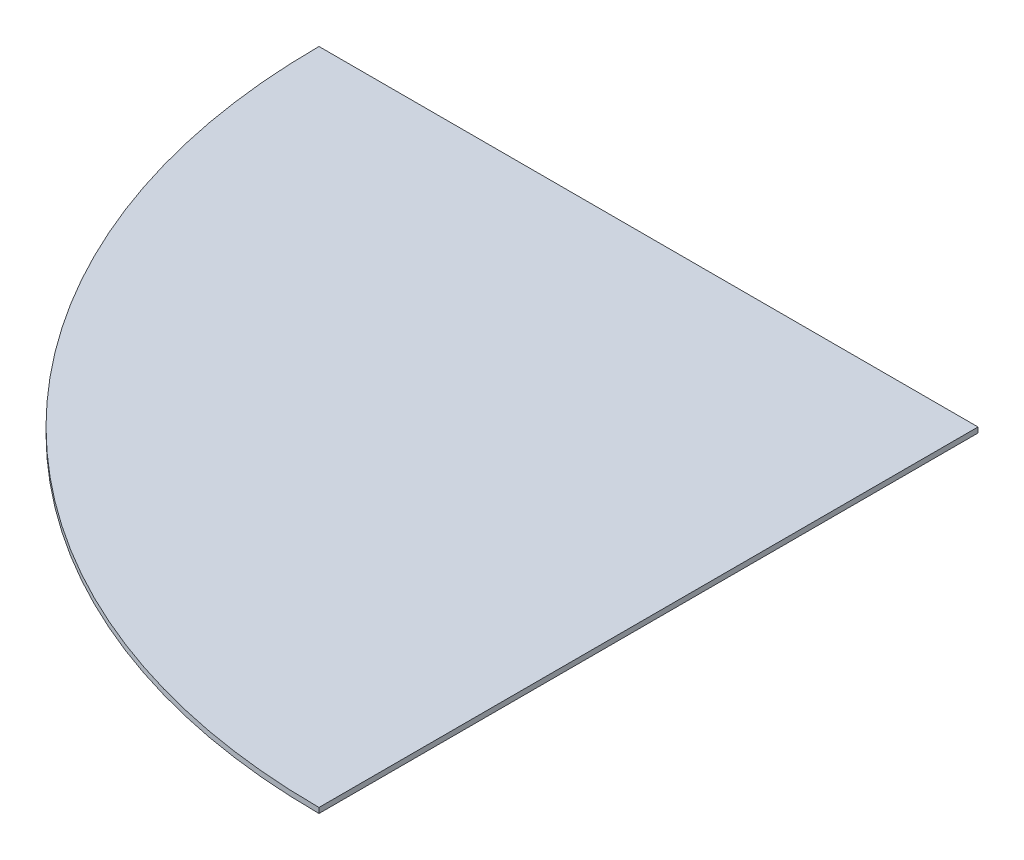
SolidWorks part; units mm, degrees
material "普通碳钢"
ref_plane "前视基准面" through (0, 0, 0) normal (0, 0, 1) x (1, 0, 0)
ref_plane "上视基准面" through (0, 0, 0) normal (0, 1, 0) x (1, 0, 0)
ref_plane "右视基准面" through (0, 0, 0) normal (1, 0, 0) x (0, 0, -1)
ref_plane "基准面1" through (0, 500, 0) normal (0, 1, 0) x (1, 0, 0)
sketch "草图1" plane through (0, 0, 0) normal (0, 1, 0) x (1, 0, 0)
  line L0 (-92.5, 0) -> (92.5, 0) construction
  line L1 (0, -92.5) -> (0, 92.5) construction
  line L2 (-92.5, 0) -> (-92.5, -92.5) construction
  line L3 (-92.5, -92.5) -> (0, -92.5) construction
  line L4 (-92.5, -92.5) -> (-592.5, -92.5) construction
  line L5 (-92.5, -92.5) -> (-92.5, -592.5) construction
  line L6 (-592.5, -92.5) -> (-92.5, -92.5)
  line L7 (-92.5, -92.5) -> (-92.5, -592.5)
  circle A0 centre (-92.5, -92.5) radius 500 construction
  arc A1 (-592.5, -92.5) -> (-92.5, -592.5) centre (-92.5, -92.5) ccw
  dimension "D5" = 500
  dimension "D3" = 1000
  dimension "D1" = 185
  dimension "D2" = 185
  dimension "D4" = 500
sketch "草图4" plane through (0, 500, 0) normal (0, 1, 0) x (1, 0, 0)
  line L0 (0, 92.5) -> (0, -92.5) construction
  line L1 (-92.5, 0) -> (92.5, 0) construction
  line L2 (-92.5, 0) -> (-92.5, -92.5) construction
  line L3 (-92.5, -92.5) -> (0, -92.5) construction
  line L4 (-92.5, -92.5) -> (-342.5, -92.5) construction
  line L5 (-92.5, -92.5) -> (-92.5, -342.5) construction
  line L6 (-92.5, -92.5) -> (-342.5, -92.5)
  line L7 (-92.5, -92.5) -> (-92.5, -342.5)
  circle A0 centre (-92.5, -92.5) radius 250 construction
  arc A1 (-342.5, -92.5) -> (-92.5, -342.5) centre (-92.5, -92.5) ccw
  dimension "D3" = 500
  dimension "D1" = 185
  dimension "D2" = 185
  dimension "D4" = 250
  dimension "D5" = 250
base flange "基体-法兰2" sketch "草图4" thickness 2 reverse thickness direction no parameters "D1"=1
sketch "折弯-线1" plane through (0, 0, 0) normal (0, 1, 0) x (1, 0, 0)
sketch "边界框1" plane through (0, 0, 0) normal (0, 1, 0) x (1, 0, 0)
sheet metal parameters "钣金4" thickness 2 parameters "D1"=1
flat pattern "平板型式4" [suppressed]
sketch "折弯-线3" plane through (0, 0, 0) normal (0, 1, 0) x (1, 0, 0)
sketch "边界框3" [suppressed] plane through (0, 0, 0) normal (0, 1, 0) x (1, 0, 0)
